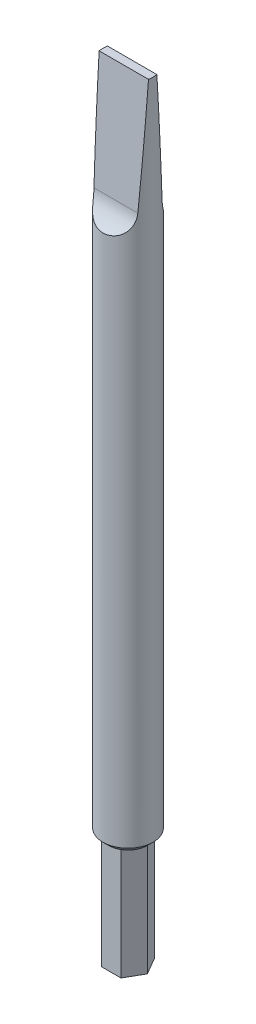
SolidWorks part; units mm, degrees
ref_plane "Front Plane" through (0, 0, 0) normal (0, 0, 1) x (1, 0, 0)
ref_plane "Top Plane" through (0, 0, 0) normal (0, 1, 0) x (1, 0, 0)
ref_plane "Right Plane" through (0, 0, 0) normal (1, 0, 0) x (0, 0, -1)
sketch "Sketch2" plane through (0, 0, 0) normal (0, 1, 0) x (1, 0, 0)
  line L7 (3.4641, 0) -> (1.7321, 3)
  line L8 (1.7321, 3) -> (-1.7321, 3)
  line L9 (-1.7321, 3) -> (-3.4641, 0)
  line L10 (-3.4641, 0) -> (-1.7321, -3)
  line L11 (-1.7321, -3) -> (1.7321, -3)
  line L12 (1.7321, -3) -> (3.4641, 0)
  circle A1 centre (0, 0) radius 3 construction
  dimension "D1" = 6
extrude "Boss-Extrude1" add sketch "Sketch2" along normal blind 20
sketch "Sketch3" plane through (0, 20, 0) normal (0, 1, 0) x (1, 0, 0)
  circle A0 centre (0, 0) radius 4.5
  dimension "D1" = 9
extrude "Boss-Extrude3" add sketch "Sketch3" along normal blind 120 separate body contours A0
chamfer "Chamfer2" distance 1 angle 45 1 edges at (0, 20, 4.5)
sketch "Sketch4" plane through (0, 140, 0) normal (0, 1, 0) x (1, 0, 0)
  line L0 (-5.388, 0) -> (7.199, 0) construction
  line L1 (-4.4371, 0.75) -> (4.4371, 0.75)
  line L2 (-4.4371, 0.75) -> (-4.4371, -0.75)
  line L3 (-4.4371, -0.75) -> (4.4371, -0.75)
  line L4 (4.4371, 0.75) -> (4.4371, -0.75)
  line L5 (14.9812, 0.75) -> (-14.9812, 0.75)
  line L6 (-14.9812, 0.75) -> (-14.9812, -0.75)
  line L7 (-14.9812, -0.75) -> (14.9812, -0.75)
  line L8 (14.9812, -0.75) -> (14.9812, 0.75)
  circle A0 centre (0, 0) radius 4.5 construction
  circle A2 centre (0, 0) radius 15
  circle M6 centre (0, 0) radius 4.5
  dimension "D2" = 30
  dimension "D1" = 1.5
extrude "Cut-Extrude2" cut sketch "Sketch4" against normal blind 25 draft 4 contours L1 M6 | L3 M6 | L5 A2 M6 | L7 A2 M6 region at (0, 140, -2.3211) region at (0, 140, -7.1386) region at (0, 140, 7.1386) region at (0, 140, 2.3211)
fillet "Fillet2" radius 5 2 edges at (0, 115, -2.4982) (0, 115, 2.4982)
